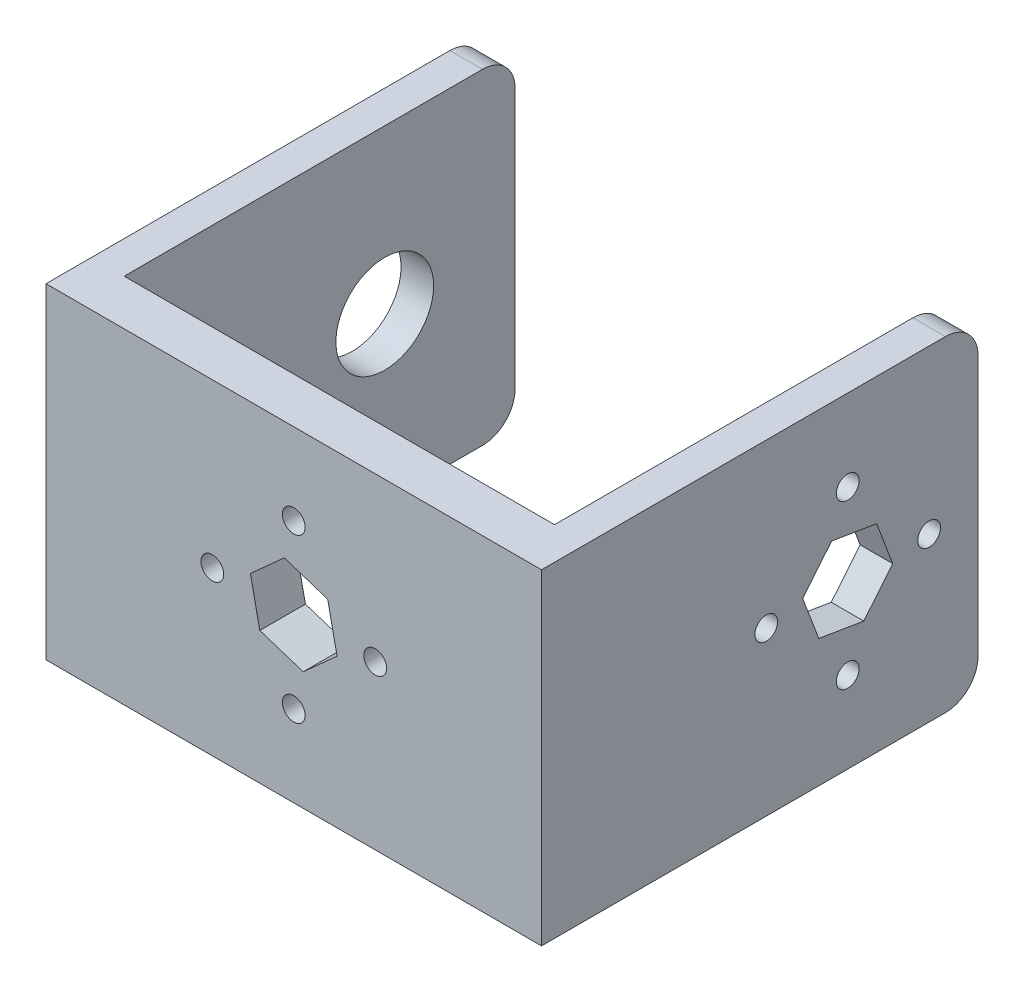
SolidWorks part; units mm, degrees
ref_plane "Front Plane" through (0, 0, 0) normal (0, 0, 1) x (1, 0, 0)
ref_plane "Top Plane" through (0, 0, 0) normal (0, 1, 0) x (1, 0, 0)
ref_plane "Right Plane" through (0, 0, 0) normal (1, 0, 0) x (0, 0, -1)
sketch "Sketch1" plane through (0, 0, 0) normal (0, 1, 0) x (1, 0, 0)
  line L0 (0, 0) -> (33.03, 0)
  line L1 (0, 0) -> (-33.03, 0)
  line L2 (-33.03, 0) -> (-33.03, 60)
  line L3 (33.03, 0) -> (33.03, 60)
  line L4 (33.03, 60) -> (38.03, 60)
  line L5 (38.03, 60) -> (38.03, -7)
  line L6 (-33.03, 60) -> (-38.03, 60)
  line L7 (-38.03, 60) -> (-38.03, -7)
  line L8 (-38.03, -7) -> (38.03, -7)
  dimension "D7" = 5
  dimension "D1" = 33.03
  dimension "D2" = 33.03
  dimension "D3" = 60
  dimension "D4" = 60
  dimension "D5" = 5
  dimension "D6" = 67
  dimension "D8" = 67
extrude "Boss-Extrude1" add sketch "Sketch1" along normal blind 50
sketch "Sketch2" plane through (-33.03, 0, 0) normal (1, 0, 0) x (0, 0, -1)
  line L0 (60, 25) -> (0, 25)
  line L1 (60, 50) -> (60, 0) construction
  line L2 (0, 50) -> (0, 0) construction
  line L3 (60, 25) -> (40, 25)
  dimension "D1" = 20
sketch "Sketch3" plane through (-33.03, 0, 0) normal (1, 0, 0) x (0, 0, -1)
  circle A0 centre (40, 25) radius 7.5
  dimension "D1" = 15
extrude "Cut-Extrude1" cut sketch "Sketch3" against normal up to surface (5 mm away) contours A0 up to face at (-38.03, 25, -26.5)
sketch "Sketch4" plane through (33.03, 0, 0) normal (-1, 0, 0) x (0, 0, 1)
  line L0 (-60, 25) -> (0, 25)
  line L1 (-60, 50) -> (-60, 0) construction
  line L2 (0, 50) -> (0, 0) construction
  line L3 (-60, 25) -> (-40, 25)
  line L5 (-46.9072, 23.8637) -> (-42.4695, 18.4501)
  line L6 (-42.4695, 18.4501) -> (-35.5624, 19.5864)
  line L7 (-35.5624, 19.5864) -> (-33.0928, 26.1363)
  line L8 (-33.0928, 26.1363) -> (-37.5305, 31.5499)
  line L9 (-37.5305, 31.5499) -> (-44.4376, 30.4136)
  line L10 (-44.4376, 30.4136) -> (-46.9072, 23.8637)
  circle A0 centre (-40, 25) radius 7
  circle A1 centre (-40, 25) radius 6.0622 construction
  circle A2 centre (-40, 25) radius 12.5
  circle A3 centre (-52.5, 25) radius 1.75
  circle A4 centre (-40, 37.5) radius 1.75
  circle A5 centre (-40, 12.5) radius 1.75
  circle A6 centre (-27.5, 25) radius 1.75
  dimension "D2" = 14
  dimension "D3" = 25
  dimension "D4" = 3.5
  dimension "D5" = 3.5
  dimension "D6" = 3.5
  dimension "D7" = 3.5
  dimension "D1" = 20
extrude "Cut-Extrude2" cut sketch "Sketch4" against normal up to surface (5 mm away) contours L5 L6 L7 L8 L9 L10 up to face at (38.03, 25, -26.5)
sketch "Sketch5" plane through (0, 0, 0) normal (0, 0, -1) x (-1, 0, 0)
  line L0 (-33.03, 25) -> (33.03, 25)
  line L1 (-33.03, 50) -> (-33.03, 0) construction
  line L2 (33.03, 50) -> (33.03, 0) construction
  line L4 (1.4517, 31.8478) -> (-5.2045, 29.6811)
  line L5 (-5.2045, 29.6811) -> (-6.6562, 22.8333)
  line L6 (-6.6562, 22.8333) -> (-1.4517, 18.1522)
  line L7 (-1.4517, 18.1522) -> (5.2045, 20.3189)
  line L8 (5.2045, 20.3189) -> (6.6562, 27.1667)
  line L9 (6.6562, 27.1667) -> (1.4517, 31.8478)
  circle A0 centre (0, 25) radius 7
  circle A1 centre (0, 25) radius 6.0622 construction
  circle A2 centre (0, 25) radius 12.5
  circle A3 centre (0, 37.5) radius 1.75
  circle A4 centre (-12.5, 25) radius 1.75
  circle A5 centre (0, 12.5) radius 1.75
  circle A6 centre (12.5, 25) radius 1.75
  dimension "D1" = 14
  dimension "D2" = 25
  dimension "D3" = 3.5
  dimension "D4" = 1.75
  dimension "D5" = 1.75
  dimension "D6" = 1.75
extrude "Cut-Extrude3" cut sketch "Sketch5" against normal up to surface (7 mm away) contours L5 L6 L7 L8 L9 L4 up to face at (0, 25, 7)
extrude "Cut-Extrude4" cut sketch "Sketch4<3>" against normal up to surface (5 mm away) contours A6 | A5 | A3 | A4 up to face at (38.03, 25, -40)
sketch "Sketch4<3>" plane through (33.03, 0, 0) normal (-1, 0, 0) x (0, 0, 1) same geometry as "Sketch4"
extrude "Cut-Extrude6" cut sketch "Sketch5<3>" against normal up to surface (7 mm away) contours A5 | A6 | A3 | A4 up to face at (0, 25, 7)
sketch "Sketch5<3>" plane through (0, 0, 0) normal (0, 0, -1) x (-1, 0, 0) same geometry as "Sketch5"
fillet "Fillet1" radius 5 4 edges at (-35.53, 50, -60) (35.53, 50, -60) (35.53, 0, -60) (-35.53, 0, -60)
